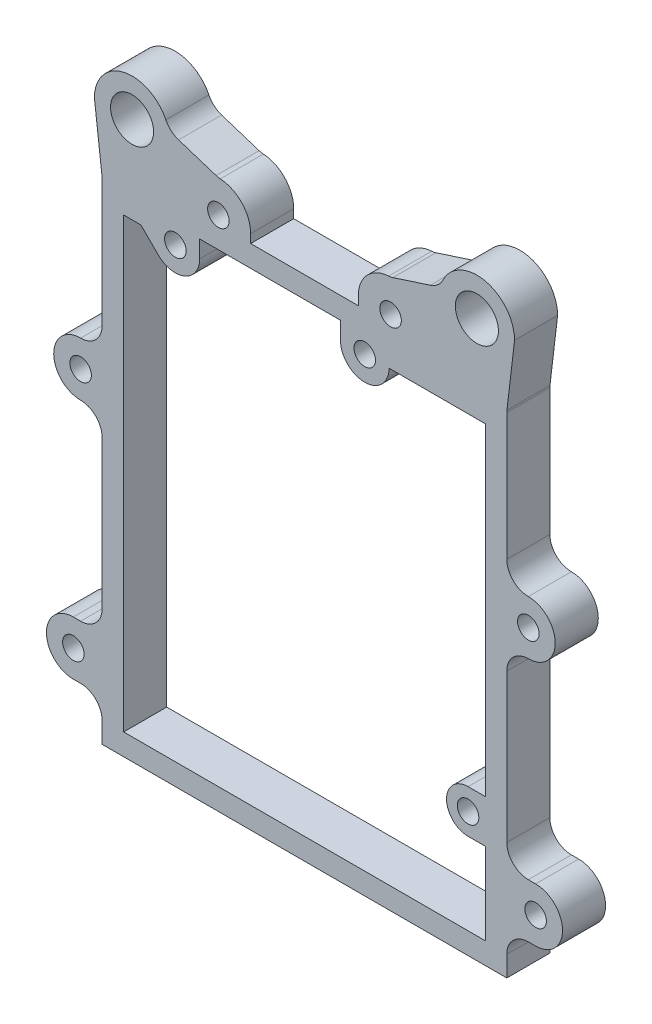
SolidWorks part; units mm, degrees
ref_plane "Front Plane" through (0, 0, 0) normal (0, 0, 1) x (1, 0, 0)
ref_plane "Top Plane" through (0, 0, 0) normal (0, 1, 0) x (1, 0, 0)
ref_plane "Right Plane" through (0, 0, 0) normal (1, 0, 0) x (0, 0, -1)
sketch "Sketch1" plane through (0, 0, 0) normal (0, 0, 1) x (1, 0, 0)
  line L0 (13.97, -3.175) -> (39.37, -3.175)
  line L2 (39.37, -3.175) -> (56.515, -3.175)
  line L3 (18.7325, 73.025) -> (18.7325, 71.755)
  line L4 (56.515, 69.215) -> (41.6251, 77.2198)
  line L5 (34.6075, 73.025) -> (34.6075, 71.755)
  line L6 (-3.175, 69.215) -> (11.7149, 77.2198)
  line L7 (34.6075, 71.755) -> (18.7325, 71.755)
  line L8 (0, 11.0938) -> (0, 16.5575)
  line L36 (53.34, 66.04) -> (53.34, 0) construction
  line L37 (53.34, 0) -> (0, 0) construction
  line L38 (0, 0) -> (0, 66.04) construction
  line L39 (0, 66.04) -> (2.54, 66.04) construction
  line L43 (40.386, 66.04) -> (53.34, 66.04) construction
  line L44 (-3.175, -3.175) -> (56.515, -3.175)
  line L45 (56.515, -3.175) -> (56.515, 69.215)
  line L46 (-3.175, 69.215) -> (-3.175, -3.175)
  line L47 (1.2249, 69.215) -> (-3.175, 69.215)
  line L48 (3.7649, 71.755) -> (1.2249, 69.215)
  line L49 (39.1611, 71.755) -> (3.7649, 71.755)
  line L50 (41.7011, 69.215) -> (39.1611, 71.755)
  line L51 (56.515, 69.215) -> (41.7011, 69.215)
  line L52 (-3.175, -3.175) -> (13.97, -3.175)
  line L53 (56.515, -3.175) -> (56.515, 69.215)
  line L54 (-3.175, 69.215) -> (-3.175, -3.175)
  line L60 (53.34, 66.04) -> (53.34, 18.415)
  line L61 (53.34, 0) -> (0, 0)
  line L62 (0, 0) -> (0, 11.0938)
  line L63 (0, 66.04) -> (2.54, 66.04)
  line L64 (26.67, -3.175) -> (26.67, 77.2177) construction
  line L66 (11.2075, 68.58) -> (31.9725, 68.58)
  line L67 (40.386, 66.04) -> (53.34, 66.04)
  line L68 (50.8, 18.415) -> (53.34, 18.415)
  line L69 (50.8, 12.065) -> (53.34, 12.065)
  line L70 (53.34, 12.065) -> (53.34, 0)
  line L74 (0, 16.5575) -> (0, 66.04)
  line L75 (5.08, 63.5065) -> (2.54, 66.04)
  line L76 (11.2075, 66.04) -> (11.2075, 68.58)
  line L77 (39.1475, 66.04) -> (40.386, 66.04)
  line L78 (31.9725, 66.04) -> (31.9725, 68.58)
  circle A0 centre (35.56, 66.04) radius 1.5875 construction
  circle A1 centre (7.62, 66.04) radius 1.5875 construction
  circle A3 centre (50.8, 15.24) radius 1.5875 construction
  circle A4 centre (35.56, 66.04) radius 1.5875
  circle A5 centre (7.62, 66.04) radius 1.5875
  circle A7 centre (50.8, 15.24) radius 1.5875
  arc A9 (50.8, 18.415) -> (50.8, 12.065) centre (50.8, 15.24) ccw
  arc A10 (5.08, 63.5065) -> (11.2075, 66.04) centre (7.62, 66.04) ccw
  arc A13 (31.9725, 66.04) -> (39.1475, 66.04) centre (35.56, 66.04) ccw
  circle A15 centre (35.56, 66.04) radius 3.5875 construction
  circle A16 centre (7.62, 66.04) radius 3.5875 construction
  circle A18 centre (39.37, 73.025) radius 1.5875
  arc A19 (41.6251, 77.2198) -> (34.6075, 73.025) centre (39.37, 73.025) ccw
  circle A20 centre (13.97, 73.025) radius 1.5875
  arc A22 (11.7149, 77.2198) -> (18.7325, 73.025) centre (13.97, 73.025) cw
  circle A24 centre (13.97, 73.025) radius 4.7625 construction
  point P20 (2.54, 13.97)
  point P29 (2.54, 13.97)
  point P34 (53.3875, 15.24)
  point P37 (6.1275, 13.97)
  point P41 (4.0581, 14.4341)
  point P47 (11.2075, 66.04)
  point P54 (39.1475, 66.04)
  point P58 (26.67, -9.525)
  point P64 (31.4325, -9.525)
  point P65 (26.67, -6.35)
  point P69 (26.67, 71.755)
  point P71 (39.37, 73.025)
  point P74 (50.4825, 73.025)
  point P75 (12.3825, 73.025)
  point P78 (31.4325, -6.35)
  dimension "D8" = 3.175
  dimension "D2" = 3.175
  dimension "D7" = 12.7
  dimension "D9" = 12.7
  dimension "D1" = 3.175
  dimension "D3" = 2
  dimension "D12" = 3.175
extrude "Boss-Extrude1" add sketch "Sketch1" along normal blind 6.35
sketch "Sketch3" plane through (0, 0, 6.35) normal (0, 0, 1) x (1, 0, 0)
  line L0 (26.67, 0) -> (26.67, 68.58) construction
  line L1 (0, 0) -> (53.34, 0) construction
  line L2 (31.9725, 68.58) -> (11.2075, 68.58) construction
  line L3 (-3.175, -3.175) -> (56.515, -3.175) construction
  line L4 (-3.175, 69.215) -> (-3.175, -3.175) construction
  line L5 (-7.4237, 10.9692) -> (-3.175, 10.9692)
  line L6 (-7.4237, 3.0317) -> (-3.175, 3.0317)
  line L7 (-3.175, 3.0317) -> (-3.175, 10.9692)
  line L8 (56.515, 3.0317) -> (56.515, 10.9692)
  line L9 (60.7637, 3.0317) -> (56.515, 3.0317)
  line L10 (60.7637, 10.9692) -> (56.515, 10.9692)
  circle A0 centre (-7.4237, 7.0005) radius 1.5875
  arc A1 (-7.4237, 10.9692) -> (-7.4237, 3.0317) centre (-7.4237, 7.0005) ccw
  arc A2 (60.7637, 10.9692) -> (60.7637, 3.0317) centre (60.7637, 7.0005) cw
  circle A3 centre (60.7637, 7.0005) radius 1.5875
  dimension "D1" = 3.175
  dimension "D2" = 10.1755
  dimension "D3" = 4.2487
extrude "Boss-Extrude2" add sketch "Sketch3" against normal up to surface (6.35 mm away) up to face at (26.67, 58.006, 0)
fillet "Fillet1" radius 3.175 4 edges
sketch "Sketch4" plane through (0, 0, 6.35) normal (0, 0, 1) x (1, 0, 0)
  line L0 (26.67, 0) -> (26.67, 68.58) construction
  line L1 (0, 0) -> (53.34, 0) construction
  line L2 (31.9725, 68.58) -> (11.2075, 68.58) construction
  line L3 (-3.175, 69.215) -> (-3.175, 14.1442) construction
  line L4 (-6.35, 47.1371) -> (-3.175, 47.1371)
  line L5 (-6.35, 39.1996) -> (-3.175, 39.1996)
  line L6 (-3.175, 39.1996) -> (-3.175, 47.1371)
  line L7 (56.515, 39.1996) -> (56.515, 47.1371)
  line L8 (59.69, 39.1996) -> (56.515, 39.1996)
  line L9 (59.69, 47.1371) -> (56.515, 47.1371)
  line L10 (4.27, 73.2174) -> (-3.175, 87.066) construction
  line L11 (11.7149, 77.2198) -> (-3.175, 69.215) construction
  line L12 (49.07, 73.2174) -> (56.515, 87.066) construction
  line L13 (-4.3181, 78.857) -> (-3.175, 69.215)
  line L14 (6.6403, 80.1562) -> (13.97, 77.7875)
  line L15 (-3.175, 69.215) -> (13.97, 77.7875)
  line L16 (56.515, 69.215) -> (39.37, 77.7875)
  line L17 (46.6997, 80.1562) -> (39.37, 77.7875)
  line L18 (57.6581, 78.857) -> (56.515, 69.215)
  circle A0 centre (-6.35, 43.1684) radius 1.5875
  arc A1 (-6.35, 47.1371) -> (-6.35, 39.1996) centre (-6.35, 43.1684) ccw
  arc A2 (59.69, 47.1371) -> (59.69, 39.1996) centre (59.69, 43.1684) cw
  circle A3 centre (59.69, 43.1684) radius 1.5875
  circle A4 centre (1.2381, 78.857) radius 3.175
  arc A5 (6.6403, 80.1562) -> (-4.1641, 77.5578) centre (1.2381, 78.857) ccw
  arc A6 (18.7325, 73.025) -> (11.7149, 77.2198) centre (13.97, 73.025) ccw construction
  arc A7 (46.6997, 80.1562) -> (57.5041, 77.5578) centre (52.1019, 78.857) cw
  circle A8 centre (52.1019, 78.857) radius 3.175
  line M20 (-3.175, 69.215) -> (-3.175, 14.1442)
  line M34 (56.515, 14.1442) -> (56.515, 69.215)
  line M35 (56.515, 69.215) -> (41.6251, 77.2198)
  arc M36 (41.6251, 77.2198) -> (34.6075, 73.025) centre (39.37, 73.025) ccw
  arc M40 (18.7325, 73.025) -> (11.7149, 77.2198) centre (13.97, 73.025) ccw
  line M41 (11.7149, 77.2198) -> (-3.175, 69.215)
  dimension "D1" = 3.175
  dimension "D2" = 3.175
  dimension "D3" = 6.35
  dimension "D4" = 11.1125
extrude "Boss-Extrude3" add sketch "Sketch4" against normal up to surface (6.35 mm away) contours L14 A5 L13 A4 M41 M40 | A7 L17 L18 A8 M36 M35 | A2 L9 L8 A3 M34 | L4 A1 L5 A0 M20 region at (-3.4334, 73.4144, 6.35) region at (-4.7625, 47.0304, 6.35) region at (49.1826, 73.4268, 6.35) region at (56.6218, 43.1684, 6.35) up to face at (26.67, 30.1848, 0)
fillet "Fillet2" radius 3.175 6 edges at (46.6997, 80.1562, 3.175) (6.6403, 80.1562, 3.175) (-3.175, 47.1371, 3.175) (56.515, 47.1371, 3.175) (56.515, 39.1996, 3.175) (-3.175, 39.1996, 3.175)
fillet "Fillet3" radius 2.54 4 edges at (-3.175, 69.215, 3.175) (13.97, 77.7875, 3.175) (56.515, 69.215, 3.175) (39.37, 77.7875, 3.175)
